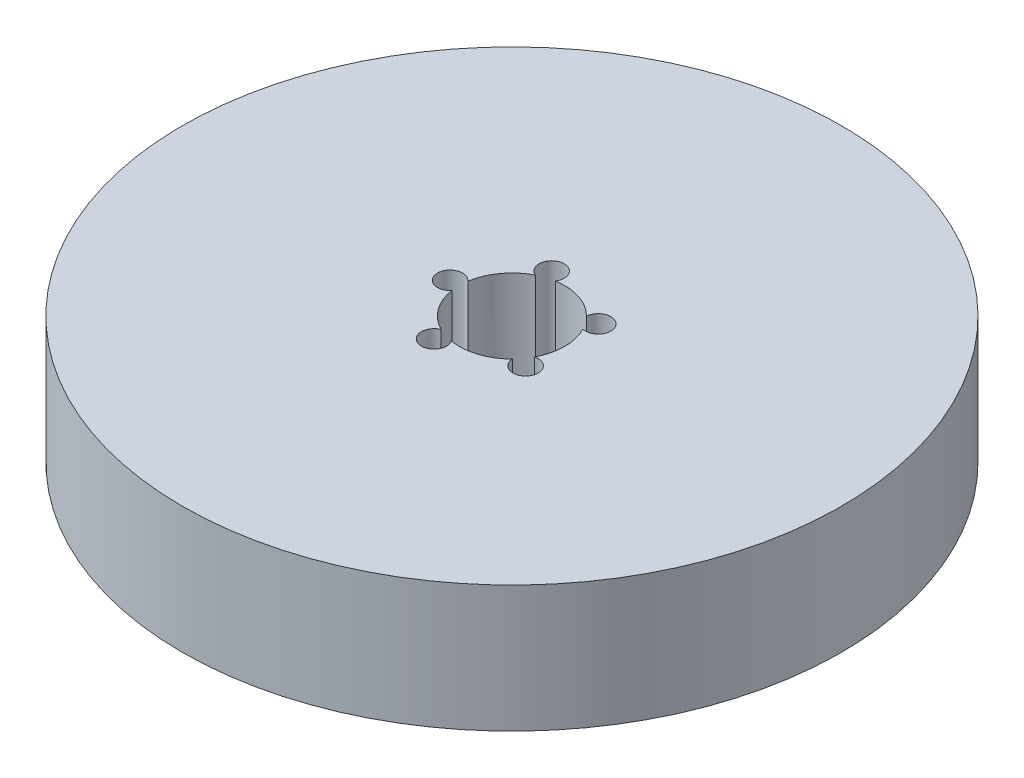
SolidWorks part; units mm, degrees
ref_plane "Front Plane" through (0, 0, 0) normal (0, 0, 1) x (1, 0, 0)
ref_plane "Top Plane" through (0, 0, 0) normal (0, 1, 0) x (1, 0, 0)
ref_plane "Right Plane" through (0, 0, 0) normal (1, 0, 0) x (0, 0, -1)
sketch "Sketch1" plane through (0, 0, 0) normal (0, 1, 0) x (1, 0, 0)
  circle A0 centre (0, 0) radius 62.5
  dimension "FLANGE_OD" = 125
extrude "Boss-Extrude1" add sketch "Sketch1" along normal blind 24
sketch "Sketch2" plane through (0, 0, 0) normal (0, 1, 0) x (1, 0, 0)
  circle A0 centre (0, 0) radius 10
  dimension "BORE_D" = 20
extrude "Cut-Extrude1" cut sketch "Sketch2" along normal through all
sketch "Sketch3" plane through (0, 24, 0) normal (0, 1, 0) x (1, 0, 0)
  circle A0 centre (0, 0) radius 11.7237 construction
  circle A1 centre (-11.7237, 0) radius 2.3843
  dimension "BOLT_D" = 4.7686
  dimension "BOLT_PCD" = 23.4475
extrude "Cut-Extrude2" cut sketch "Sketch3" against normal blind 23.8736
pattern_circular "CirPattern1" count 5 over 360 about axis through (0, 0, 0) along (0, 1, 0) of "Cut-Extrude2"
